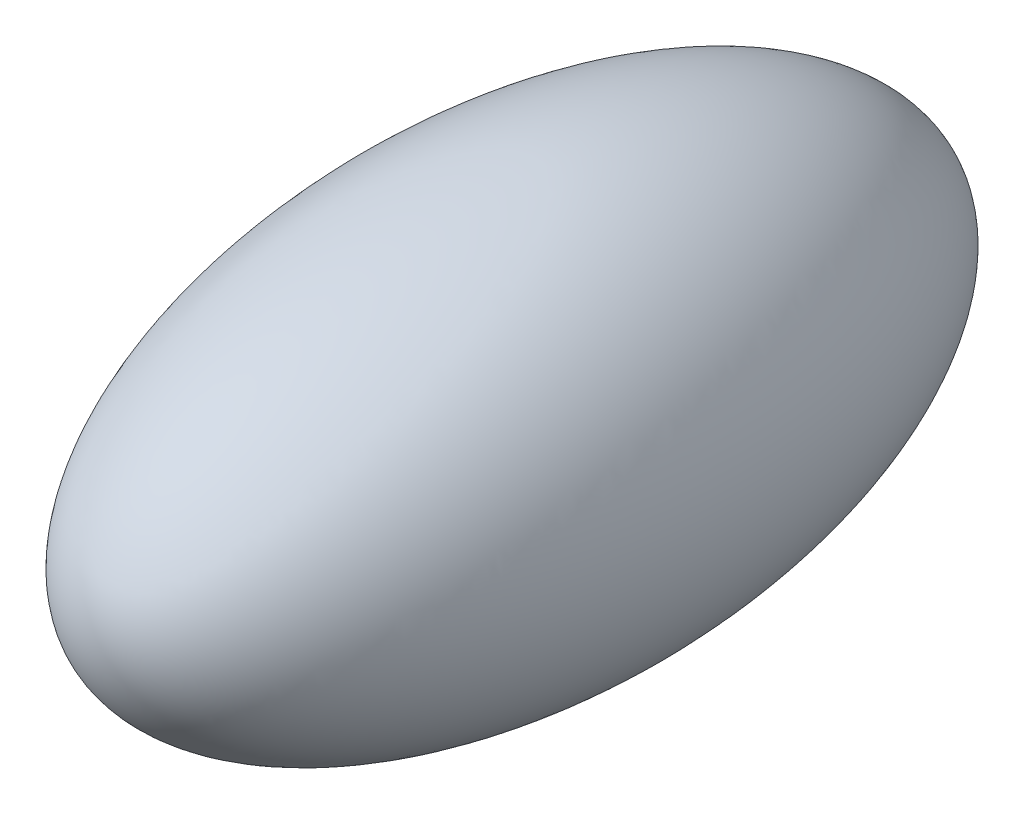
SolidWorks part; units mm, degrees
ref_plane "Front Plane" through (0, 0, 0) normal (0, 0, 1) x (1, 0, 0)
ref_plane "Top Plane" through (0, 0, 0) normal (0, 1, 0) x (1, 0, 0)
ref_plane "Right Plane" through (0, 0, 0) normal (1, 0, 0) x (0, 0, -1)
sketch "Sketch1" plane through (0, 0, 0) normal (0, 1, 0) x (1, 0, 0)
  line L0 (0, 100) -> (0, 122.057) construction
  line L1 (0, -100) -> (0, 100)
  ellipse E0 centre (0, 0) end of major axis (0, 100) minor radius 50
  dimension "D1" = 100
  dimension "D2" = 200
revolve "Revolve5" add sketch "Sketch1" angle 360 about L0 region at (21.2207, 0, 0)
